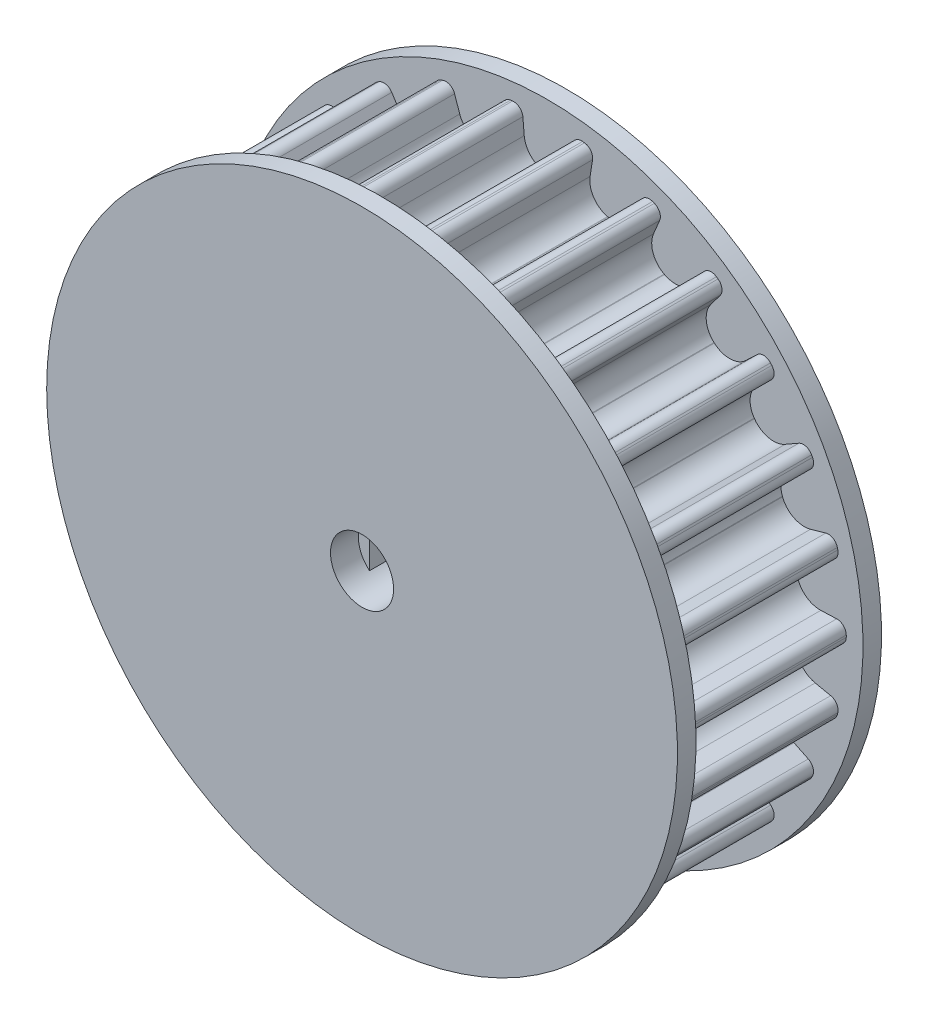
SolidWorks part; units mm, degrees
ref_plane "Front Plane" through (0, 0, 0) normal (0, 0, 1) x (1, 0, 0)
ref_plane "Top Plane" through (0, 0, 0) normal (0, 1, 0) x (1, 0, 0)
ref_plane "Right Plane" through (0, 0, 0) normal (1, 0, 0) x (0, 0, -1)
sketch "Sketch1" plane through (0, 0, 0) normal (0, 0, 1) x (1, 0, 0)
  circle A0 centre (0, 0) radius 32.2
  dimension "D1" = 64.4
extrude "Boss-Extrude1" add sketch "Sketch1" along normal mid plane 18
sketch "Sketch2" plane through (0, 0, 9) normal (0, 0, 1) x (1, 0, 0)
  line L0 (-2.75, 32.0824) -> (-2.3214, 27.0824)
  line L1 (-2.3214, 27.0824) -> (2.3214, 27.0824)
  line L2 (0, -55) -> (0, 55) construction
  line L3 (0, 0) -> (-2.75, 32.0824) construction
  line L4 (2.75, 32.0824) -> (2.3214, 27.0824)
  circle A0 centre (0, 0) radius 32.2 construction
  arc A1 (-2.75, 32.0824) -> (2.75, 32.0824) centre (0, 32.3181) cw
  point P8 (0, 27.0824)
  dimension "D1" = 5
  dimension "D2" = 5.5
extrude "Cut-Extrude2" cut sketch "Sketch2" against normal up to next
fillet "Fillet1" radius 2.5 2 edges at (2.3214, 27.0824, 0) (-2.3214, 27.0824, 0)
fillet "Fillet2" radius 1 2 edges at (2.75, 32.0824, 0) (-2.75, 32.0824, 0)
ref_axis "Axis1" through (0, 0, -7.7129) along (0, 0, 1)
pattern_circular "CirPattern1" count 26 over 360 about axis through (0, 0, -7.7129) along (0, 0, 1) of "Fillet1", "Cut-Extrude2", "Fillet2"
sketch "Sketch3" plane through (0, 0, -9) normal (0, 0, -1) x (-1, 0, 0)
  circle A0 centre (0, 0) radius 34
  dimension "D1" = 68
extrude "Boss-Extrude2" add sketch "Sketch3" along normal blind 2
mirror "Mirror1" about plane through (0, 0, 0) normal (0, 0, 1) of "Boss-Extrude2"
sketch "Sketch4" plane through (0, 0, -11) normal (0, 0, -1) x (-1, 0, 0)
  line L0 (2.2, -2.5923) -> (2.2, 2.5923)
  arc A0 (2.2, -2.5923) -> (2.2, 2.5923) centre (0, 0) cw
  dimension "D1" = 3.4
  dimension "D2" = 2.2
extrude "Cut-Extrude3" cut sketch "Sketch4" against normal through all
sketch "Sketch5" plane through (0, 0, -11) normal (0, 0, -1) x (-1, 0, 0)
  line L0 (12.1, 0) -> (-12.1, 0) construction
  line L1 (8.5892, -2.5) -> (5.5892, -2.5)
  line L2 (8.5892, -2.5) -> (8.5892, 2.5)
  line L3 (8.5892, 2.5) -> (5.5892, 2.5)
  line L4 (5.5892, -2.5) -> (5.5892, 2.5)
  line L5 (8.5892, -2.5) -> (5.5892, 2.5) construction
  line L6 (8.5892, 2.5) -> (5.5892, -2.5) construction
  point P0 (7.0892, 0)
  dimension "D1" = 3
  dimension "D2" = 5
extrude "Cut-Extrude4" cut sketch "Sketch5" against normal blind 18.5
ref_plane "Plane1" through (-35.5892, 0, 0) normal (-1, 0, 0) x (0, 0, 1)
sketch "Sketch6" plane through (-35.5892, 0, 0) normal (-1, 0, 0) x (0, 0, 1)
  line L1 (12.1, 0) -> (-12.1, 0) construction
  circle A0 centre (2.5, 0) radius 3
  point P3 (0, 0)
  dimension "D1" = 2.5
extrude "Cut-Extrude5" cut sketch "Sketch6" against normal blind 18
sketch "Sketch8" plane through (-35.5892, 0, 0) normal (-1, 0, 0) x (0, 0, 1)
  circle A0 centre (2.5, 0) radius 1.55
extrude "Cut-Extrude6" cut sketch "Sketch8" against normal blind 35
sketch "Sketch9" plane through (0, 0, 11) normal (0, 0, 1) x (1, 0, 0)
  circle A0 centre (0, 0) radius 3.4
  line M2 (-2.2, -2.5923) -> (-2.2, 2.5923)
extrude "Cut-Extrude7" cut sketch "Sketch9" against normal blind 3 contours A0 M2 region at (-2.6881, 0, 11)
